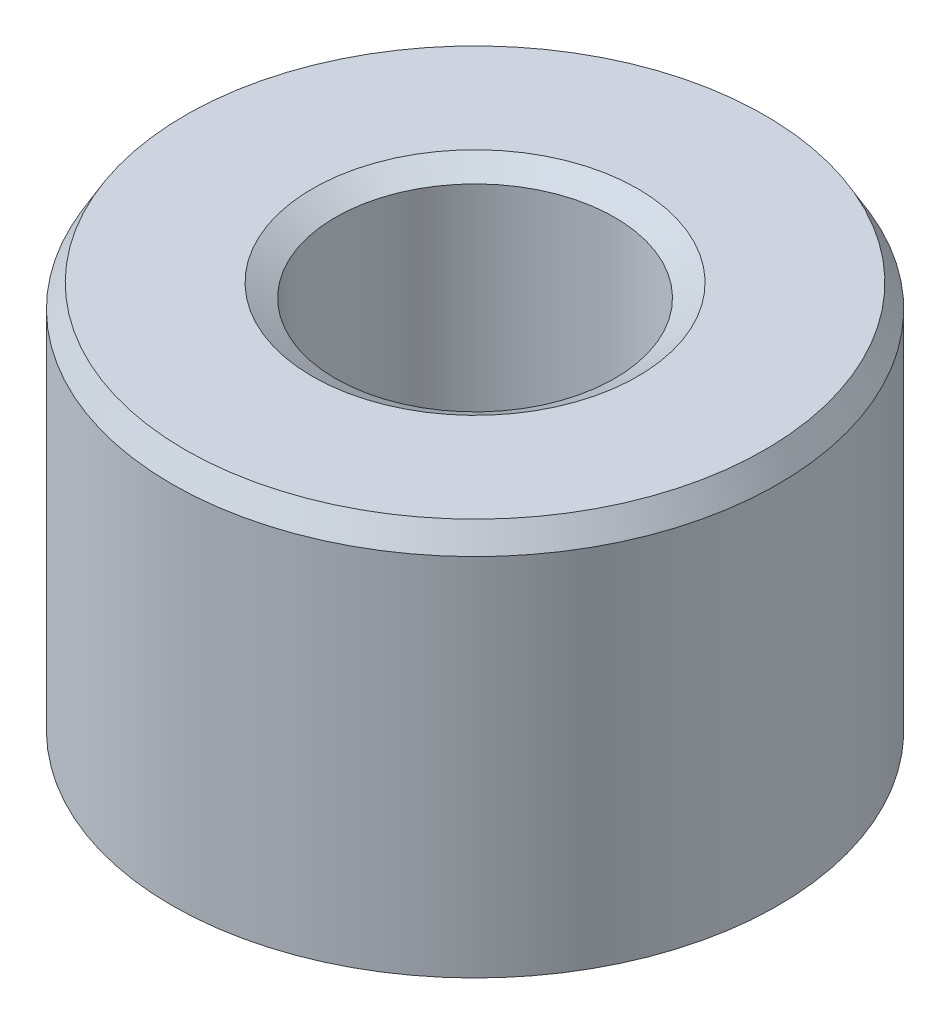
SolidWorks part; units mm, degrees
ref_plane "Front Plane" through (0, 0, 0) normal (0, 0, 1) x (1, 0, 0)
ref_plane "Top Plane" through (0, 0, 0) normal (0, 1, 0) x (1, 0, 0)
ref_plane "Right Plane" through (0, 0, 0) normal (1, 0, 0) x (0, 0, -1)
sketch "Sketch1" plane through (0, 0, 0) normal (0, 1, 0) x (1, 0, 0)
  circle A0 centre (0, 0) radius 5
  dimension "SLEEVE_OD" = 10
extrude "Boss-Extrude1" add sketch "Sketch1" along normal blind 6.6188
sketch "Sketch2" plane through (0, 0, 0) normal (0, 1, 0) x (1, 0, 0)
  circle A0 centre (0, 0) radius 2.3034
  dimension "BORE_D" = 4.6069
extrude "Cut-Extrude1" cut sketch "Sketch2" along normal through all
chamfer "Chamfer1" distance 0.3799 angle 30 4 edges at (0, 6.6188, 2.3034) (0, 0, 2.3034) (0, 0, 5) (0, 6.6188, 5) first distance on face at (0, 6.6188, 2.3034) first distance on face at (0, 0, 2.3034) first distance on face at (0, 6.6188, 5)
